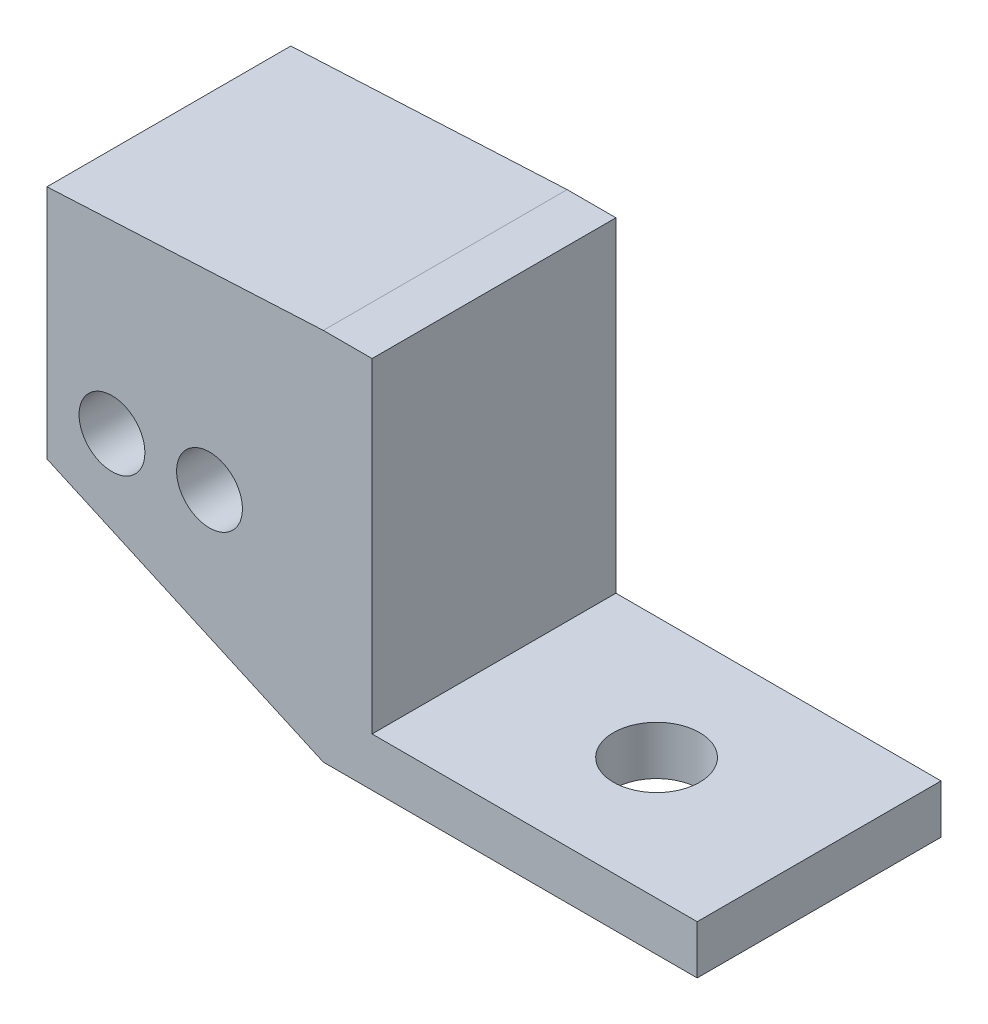
SolidWorks part; units mm, degrees
ref_plane "Front Plane" through (0, 0, 0) normal (0, 0, 1) x (1, 0, 0)
ref_plane "Top Plane" through (0, 0, 0) normal (0, 1, 0) x (1, 0, 0)
ref_plane "Right Plane" through (0, 0, 0) normal (1, 0, 0) x (0, 0, -1)
sketch "Sketch1" plane through (0, 0, 0) normal (0, 0, 1) x (1, 0, 0)
  line L0 (53.4899, -84.3159) -> (59.4899, -84.3159) construction
  line L1 (56.4899, -84.3159) -> (66.4899, -84.3159) construction
  line L2 (66.4899, -72.3159) -> (69.4899, -72.3159)
  line L3 (56.4899, -77.3159) -> (56.4899, -84.3159) construction
  line L4 (49.4899, -73.1659) -> (49.4899, -87.6659)
  line L7 (66.4899, -95.3159) -> (89.4899, -95.3159)
  line L9 (69.4899, -72.3159) -> (69.4899, -92.3159)
  line L10 (69.4899, -92.3159) -> (89.4899, -92.3159)
  line L11 (89.4899, -92.3159) -> (89.4899, -95.3159)
  line L14 (49.4899, -87.6659) -> (66.4899, -95.3159)
  line L17 (56.4899, -77.3159) -> (66.4899, -77.3159) construction
  line L18 (66.4899, -72.3159) -> (49.4899, -73.1659)
  line L19 (56.4899, -84.3159) -> (56.4899, -90.8159) construction
  line L20 (56.4899, -84.3159) -> (49.4899, -84.3159) construction
  line L21 (56.4899, -84.3159) -> (56.4899, -72.8159) construction
  line L22 (66.4899, -77.3159) -> (66.4899, -95.3159) construction
  line L23 (89.4899, 311.6195) -> (89.4899, -188.3805) construction
  circle A0 centre (56.4899, -77.3159) radius 3.025
  circle A1 centre (53.4899, -84.3159) radius 2.025
  circle A2 centre (59.4899, -84.3159) radius 2.025
  point P1 (123.2137, -84.3159)
  point P3 (88.2378, -93.2239)
  point P6 (64.3492, -70.1933)
  point P10 (40.5927, -84.3159)
  point P11 (102.4549, -84.3159)
  point P12 (89.4899, -92.8967)
  point P15 (41.4899, -89.6101)
  point P27 (96.8542, -90.1402)
  dimension "D3" = 4.05
  dimension "D4" = 6.05
  dimension "D1" = 3
  dimension "D2" = 6
  dimension "D5" = 6.5
  dimension "D6" = 7
  dimension "D7" = 11.5
  dimension "D8" = 23
  dimension "D9" = 17
  dimension "D10" = 20
  dimension "D11" = 20
  dimension "D12" = 8
extrude "Boss-Extrude1" add sketch "Sketch1" along normal blind 15
extrude "Boss-Extrude2" add sketch "Sketch1<2>" along normal up to surface (15 mm away) from offset 6 contours A0 region at (56.4899, -77.3159, 0) up to face at (55.5149, -84.3159, 15)
sketch "Sketch1<2>" plane through (0, 0, 0) normal (0, 0, 1) x (1, 0, 0) same geometry as "Sketch1"
sketch "Sketch2" plane through (0, -95.3159, 0) normal (0, -1, 0) x (1, 0, 0)
  line L0 (89.4899, 0) -> (69.4899, 15) construction
  line L1 (66.4899, 15) -> (89.4899, 15) construction
  line L2 (69.4899, 15) -> (89.4899, 15) construction
  circle A0 centre (79.4899, 7.5) radius 2.65
  dimension "D2" = 5.3
  dimension "D1" = 20
extrude "Cut-Extrude1" cut sketch "Sketch2" against normal up to surface (3 mm away) up to face at (79.4899, -92.3159, 7.5)
